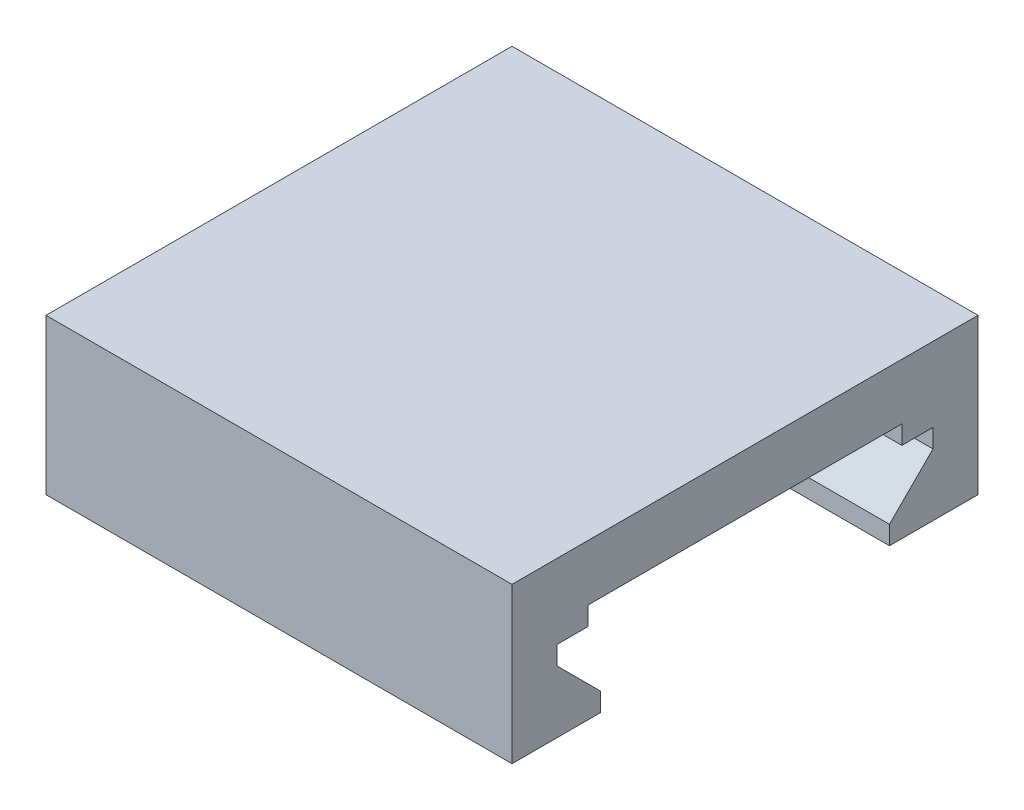
SolidWorks part; units mm, degrees
ref_plane "Front Plane" through (0, 0, 0) normal (0, 0, 1) x (1, 0, 0)
ref_plane "Top Plane" through (0, 0, 0) normal (0, 1, 0) x (1, 0, 0)
ref_plane "Right Plane" through (0, 0, 0) normal (1, 0, 0) x (0, 0, -1)
sketch "Master Design Profile" plane through (0, 0, 0) normal (1, 0, 0) x (0, 0, -1)
  line L0 (-5.05, 5.3923) -> (5.05, 5.3923)
  line L1 (12, 0) -> (6, 10.3923)
  line L2 (6, 10.3923) -> (-6, 10.3923)
  line L3 (-6, 10.3923) -> (-12, 0)
  line L4 (-12, 0) -> (-8.9579, -5.2691)
  line L5 (0, -10.3923) -> (6, -10.3923) construction
  line L6 (8.9579, -5.2691) -> (12, 0)
  line L7 (-5.05, 5.3923) -> (-5.05, 4.7923)
  line L8 (-5.05, 4.7923) -> (-6.05, 4.7923)
  line L9 (0, -28.6883) -> (0, 28.6883) construction
  line L10 (-6.05, 4.7923) -> (-6.05, 4.1923)
  line L11 (-6.05, 4.1923) -> (-4.65, 2.7923)
  line L13 (-4.65, 2.7923) -> (-4.65, 2.1923)
  line L14 (-4.65, 2.1923) -> (-8.9579, -5.2691)
  line L15 (4.65, 2.1923) -> (8.9579, -5.2691)
  line L16 (4.65, 2.7923) -> (4.65, 2.1923)
  line L17 (6.05, 4.1923) -> (4.65, 2.7923)
  line L18 (6.05, 4.7923) -> (6.05, 4.1923)
  line L19 (5.05, 4.7923) -> (6.05, 4.7923)
  line L20 (5.05, 5.3923) -> (5.05, 4.7923)
  line L21 (-9, -5.1962) -> (-6, -10.3923) construction
  line L22 (-8.9579, -5.2691) -> (-9, -5.1962) construction
  line L23 (-6, -10.3923) -> (0, -10.3923) construction
  line L24 (6, -10.3923) -> (9, -5.1962) construction
  line L25 (9, -5.1962) -> (8.9579, -5.2691) construction
  circle A0 centre (0, 0) radius 10.3923 construction
  point P15 (0, 0)
  point P16 (0, 5.3923)
  dimension "D1" = 10.1
  dimension "D2" = 0.6
  dimension "D3" = 0.6
  dimension "D4" = 1
  dimension "D5" = 135
  dimension "D6" = 2
  dimension "D7" = 5
  dimension "D8" = 210
  dimension "D9" = 0.6
  dimension "D10" = 12
sketch "LED Groove Profile Test" plane through (0, 0, 0) normal (1, 0, 0) x (0, 0, -1)
  line L0 (4.65, 2.7923) -> (4.65, 2.1923) construction
  line L1 (6.05, 4.1923) -> (4.65, 2.7923) construction
  line L2 (6.05, 4.7923) -> (6.05, 4.1923) construction
  line L3 (5.05, 4.7923) -> (6.05, 4.7923) construction
  line L4 (5.05, 5.3923) -> (5.05, 4.7923) construction
  line L5 (-5.05, 5.3923) -> (5.05, 5.3923) construction
  line L6 (-5.05, 5.3923) -> (-5.05, 4.7923) construction
  line L7 (-5.05, 4.7923) -> (-6.05, 4.7923) construction
  line L8 (-6.05, 4.7923) -> (-6.05, 4.1923) construction
  line L9 (-6.05, 4.1923) -> (-4.65, 2.7923) construction
  line L10 (-4.65, 2.7923) -> (-4.65, 2.1923) construction
  line L11 (-4.65, 2.7923) -> (-4.65, 2.1923)
  line L12 (-6.05, 4.1923) -> (-4.65, 2.7923)
  line L13 (-6.05, 4.7923) -> (-6.05, 4.1923)
  line L14 (-5.05, 4.7923) -> (-6.05, 4.7923)
  line L15 (-5.05, 5.3923) -> (-5.05, 4.7923)
  line L16 (-5.05, 5.3923) -> (5.05, 5.3923)
  line L17 (5.05, 5.3923) -> (5.05, 4.7923)
  line L18 (5.05, 4.7923) -> (6.05, 4.7923)
  line L19 (6.05, 4.7923) -> (6.05, 4.1923)
  line L20 (6.05, 4.1923) -> (4.65, 2.7923)
  line L21 (4.65, 2.7923) -> (4.65, 2.1923)
  line L22 (-4.65, 2.1923) -> (-7.5, 2.1923)
  line L23 (-7.5, 2.1923) -> (-7.5, 7.1923)
  line L24 (-7.5, 7.1923) -> (7.5, 7.1923)
  line L25 (7.5, 7.1923) -> (7.5, 2.1923)
  line L26 (7.5, 2.1923) -> (4.65, 2.1923)
  line L27 (0, -28.6883) -> (0, 28.6883) construction
  point P0 (0, 7.1923)
  dimension "D1" = 5
  dimension "D2" = 15
extrude "Boss-Extrude1" add sketch "LED Groove Profile Test" along normal mid plane 15
